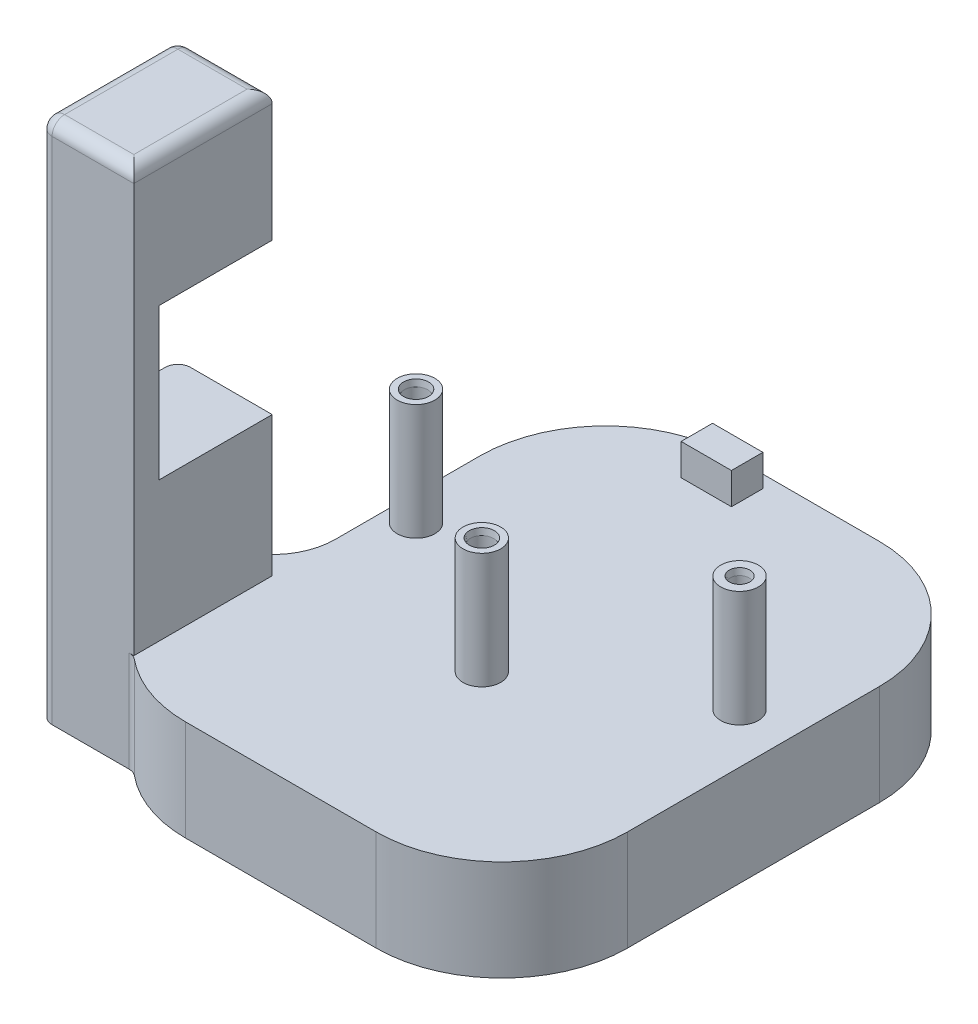
SolidWorks part; units mm, degrees
ref_plane "Front Plane" through (0, 0, 0) normal (0, 0, 1) x (1, 0, 0)
ref_plane "Top Plane" through (0, 0, 0) normal (0, 1, 0) x (1, 0, 0)
ref_plane "Right Plane" through (0, 0, 0) normal (1, 0, 0) x (0, 0, -1)
sketch "Sketch5" plane through (0, 0, 0) normal (0, 1, 0) x (1, 0, 0)
  line L1 (31.75, 40) -> (-31.75, 40)
  line L2 (31.75, 40) -> (31.75, -40)
  line L3 (31.75, -40) -> (-31.75, -40)
  line L4 (-31.75, 40) -> (-31.75, -40)
  line L5 (31.75, 40) -> (-31.75, -40) construction
  line L6 (31.75, -40) -> (-31.75, 40) construction
  point P0 (0, 0)
  dimension "D1" = 80
  dimension "D2" = 63.5
extrude "Boss-Extrude4" add sketch "Sketch5" along normal blind 16
sketch "Sketch6" plane through (0, 16, 0) normal (0, 1, 0) x (1, 0, 0)
  line L0 (31.75, 40) -> (-31.75, 40) construction
  line L1 (-4.75, 38) -> (-12.75, 38)
  line L2 (-4.75, 38) -> (-4.75, 33)
  line L3 (-4.75, 33) -> (-12.75, 33)
  line L4 (-12.75, 38) -> (-12.75, 33)
  line L5 (-4.75, 38) -> (-12.75, 33) construction
  line L6 (-4.75, 33) -> (-12.75, 38) construction
  line L9 (0, 0) -> (0, 40) construction
  line L10 (-31.75, 40) -> (-31.75, -40) construction
  point P0 (-8.75, 35.5)
  dimension "D1" = 8
  dimension "D2" = 5
  dimension "D3" = 2
  dimension "D4" = 19
extrude "Boss-Extrude5" add sketch "Sketch6" along normal blind 5 contours L3 L4 L1 L2
sketch "Sketch9" plane through (0, 0, 0) normal (0, 1, 0) x (1, 0, 0)
  line L0 (-31.75, 40) -> (-31.75, -40) construction
  line L5 (-31.75, -35) -> (-46.75, -35)
  line L6 (-31.75, -35) -> (-31.75, -13)
  line L7 (-31.75, -13) -> (-46.75, -13)
  line L8 (-46.75, -35) -> (-46.75, -13)
  line L9 (-31.75, -40) -> (31.75, -40) construction
  point P13 (-39.25, -13)
  dimension "D4" = 5
  dimension "D5" = 22
  dimension "D6" = 7.5
sketch "Sketch13" plane through (0, 16, 0) normal (0, 1, 0) x (1, 0, 0)
  line L0 (-31.75, 40) -> (-31.75, -40) construction
  line L2 (-31.75, -40) -> (31.75, -40) construction
  circle A0 centre (-27.6098, 5.72) radius 3
  circle A1 centre (23.8252, 5.72) radius 3
  circle A2 centre (-1.905, -9.52) radius 3
  dimension "D1" = 4.1402
  dimension "D3" = 6
  dimension "D4" = 51.435
  dimension "D6" = 6
  dimension "D7" = 6
  dimension "D2" = 45.72
  dimension "D5" = 45.72
  dimension "D8" = 25.7048
  dimension "D9" = 15.24
extrude "Boss-Extrude8" add sketch "Sketch13" along normal blind 18.4
extrude "Boss-Extrude10" add sketch "Sketch9" along normal blind 83 contours L8 L7 L6 L5
sketch "Sketch14" plane through (0, 0, 13) normal (0, 0, -1) x (-1, 0, 0)
  line L0 (31.75, 83) -> (31.75, 16) construction
  line L1 (31.75, 38.2) -> (46.75, 38.2)
  line L2 (31.75, 38.2) -> (31.75, 62.2)
  line L3 (31.75, 62.2) -> (46.75, 62.2)
  line L4 (46.75, 38.2) -> (46.75, 62.2)
  line L5 (46.75, 83) -> (46.75, 0) construction
  line L6 (31.75, 83) -> (46.75, 83) construction
  dimension "D1" = 20.8
  dimension "D2" = 24
extrude "Cut-Extrude1" cut sketch "Sketch14" against normal blind 18 contours L3 L4 L1 L2
fillet "Fillet1" radius 20 4 edges at (-31.75, 8, -40) (31.75, 8, -40) (-31.75, 8, 40) (31.75, 8, 40)
fillet "Fillet2" radius 10 1 edges at (-31.75, 8, 13)
fillet "Fillet3" radius 2 3 edges at (-31.75, 8, 35) (-46.75, 41.5, 35) (-46.75, 19.1, 13)
fillet "Fillet4" radius 2 1 edges at (-46.75, 72.6, 13)
fillet "Fillet6" radius 2 6 edges at (-31.75, 83, 24) (-38.25, 83, 35) (-46.1642, 83, 34.4142) (-46.75, 83, 24) (-46.1642, 83, 13.5858) (-38.25, 83, 13)
sketch "Sketch15" plane through (0, 34.4, 0) normal (0, 1, 0) x (1, 0, 0)
  circle A0 centre (23.8252, 5.72) radius 1.6383
  circle A1 centre (23.8252, 5.72) radius 3 construction
  circle A2 centre (-1.905, -9.52) radius 2
  circle A5 centre (-27.6098, 5.72) radius 2
  dimension "D1" = 3.2766
  dimension "D3" = 4
  dimension "D4" = 4
  dimension "D2" = 0
extrude "Cut-Extrude2" cut sketch "Sketch15" against normal blind 1 draft 8
sketch "Sketch16" plane through (0, 33.4, 0) normal (0, 1, 0) x (1, 0, 0)
  circle A0 centre (23.8252, 5.72) radius 1.4986
  circle A1 centre (23.8252, 5.72) radius 3 construction
  circle A2 centre (-1.905, -9.52) radius 2
  circle A3 centre (-27.6098, 5.72) radius 2
  dimension "D1" = 2.9972
  dimension "D3" = 4
  dimension "D4" = 4
  dimension "D2" = 0
extrude "Cut-Extrude3" cut sketch "Sketch16" against normal blind 7
